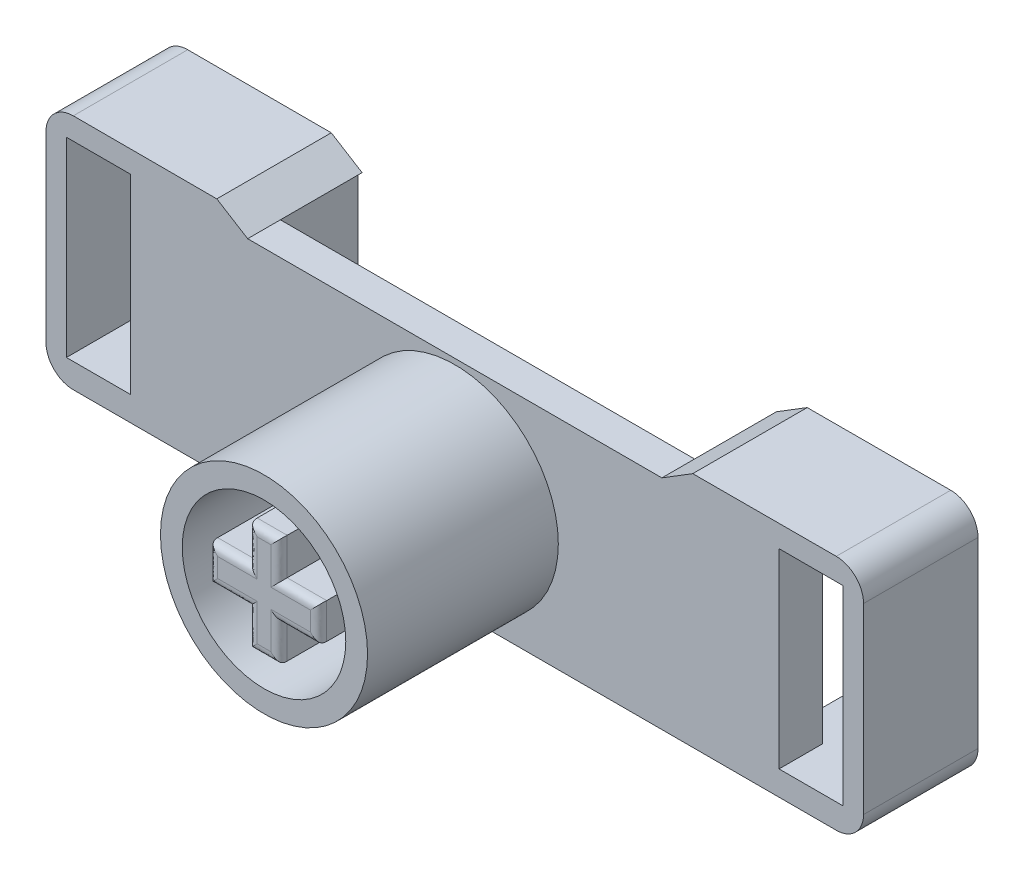
SolidWorks part; units mm, degrees
ref_plane "Front Plane" through (0, 0, 0) normal (0, 0, 1) x (1, 0, 0)
ref_plane "Top Plane" through (0, 0, 0) normal (0, 1, 0) x (1, 0, 0)
ref_plane "Right Plane" through (0, 0, 0) normal (1, 0, 0) x (0, 0, -1)
sketch "Cherry" plane through (0, 0, 0) normal (0, 0, 1) x (1, 0, 0)
  line L0 (0.55, 0.65) -> (2, 0.65)
  line L1 (-2, -0.65) -> (-0.55, -0.65)
  line L2 (-2, -0.65) -> (-2, 0.65)
  line L3 (-2, 0.65) -> (-0.55, 0.65)
  line L4 (2, -0.65) -> (2, 0.65)
  line L7 (-0.55, -2) -> (0.55, -2)
  line L8 (-0.55, -2) -> (-0.55, -0.65)
  line L9 (-0.55, 2) -> (0.55, 2)
  line L10 (0.55, -2) -> (0.55, -0.65)
  line L13 (0.55, 0.65) -> (0.55, 2)
  line L15 (0.55, -0.65) -> (2, -0.65)
  line L17 (-0.55, 0.65) -> (-0.55, 2)
  circle A0 centre (0, 0) radius 3
  circle A1 centre (0, 0) radius 3.8
  dimension "D1" = 1.3
  dimension "D2" = 4
  dimension "D3" = 1.1
  dimension "D4" = 4
extrude "Outer Cylinder" add sketch "Cherry" along normal blind 7 contours A1 A0 | L17 L3 L2 L1 L8 L7 L10 L15 L4 L0 L13 L9 region at (0, 0, 0) region at (-3.6925, 0, 0)
sketch "Inner Gap" plane through (0, 0, 0) normal (0, 0, 1) x (1, 0, 0)
  circle A0 centre (0, 0.0112) radius 3
extrude "Inner Wall" add sketch "Inner Gap" along normal blind 3
fillet "Fillet2" radius 0.3 12 edges at (-1.275, 0.65, 7) (-2, 0, 7) (-1.275, -0.65, 7) (-0.55, -1.325, 7) (0, -2, 7) (0.55, -1.325, 7) (1.275, -0.65, 7) (2, 0, 7) (1.275, 0.65, 7) (0.55, 1.325, 7) (0, 2, 7) (-0.55, 1.325, 7) curvature continuous yes
sketch "Sketch2" plane through (0, 0, 0) normal (0, 0, 1) x (1, 0, 0)
  line L5 (0, -1000) -> (0, 49000) construction
  line L6 (-1000, 0) -> (49000, 0) construction
  line L7 (-15, -996.1639) -> (-15, 49003.8361) construction
  line L8 (-11.55, -997.4571) -> (-11.55, 49002.5429) construction
  line L9 (-14.1, -997.5605) -> (-14.1, 49002.4395) construction
  line L10 (-7.6, -998.1554) -> (-7.6, 49001.8446) construction
  line L12 (-1001.5043, 4) -> (48998.4957, 4) construction
  line L14 (-1001.5043, -4) -> (48998.4957, -4) construction
  line L21 (-1004.1116, 4.7) -> (48995.8884, 4.7) construction
  line L22 (-15, -3) -> (-15, 3.706)
  line L24 (-13.9989, 4.706) -> (-8.7319, 4.7)
  line L28 (-7.6, 4) -> (7.6, 4)
  line L29 (-14, -4) -> (14, -4)
  line L30 (-8.6, -997.4752) -> (-8.6, 49002.5248) construction
  line L31 (-8.7319, 4.7) -> (-7.6, 4)
  line L32 (-1003.474, -3.1) -> (48996.526, -3.1) construction
  line L33 (-1010.3803, 3.8) -> (48989.6197, 3.8) construction
  line L38 (7.6, -998.1554) -> (7.6, 49001.8446) construction
  line L39 (8.6, -997.4752) -> (8.6, 49002.5248) construction
  line L40 (11.55, -997.4571) -> (11.55, 49002.5429) construction
  line L41 (14.1, -997.5605) -> (14.1, 49002.4395) construction
  line L42 (15, -996.1639) -> (15, 49003.8361) construction
  line L47 (8.7319, 4.7) -> (7.6, 4)
  line L48 (13.9989, 4.706) -> (8.7319, 4.7)
  line L49 (15, -3) -> (15, 3.706)
  arc A0 (15, -3) -> (14, -4) centre (14, -3) cw
  arc A1 (13.9989, 4.706) -> (15, 3.706) centre (14, 3.706) cw
  arc A2 (-15, -3) -> (-14, -4) centre (-14, -3) ccw
  arc A3 (-15, 3.706) -> (-13.9989, 4.706) centre (-14, 3.706) cw
  point P41 (0, 4)
  point P69 (0, -4)
  point P71 (15, -4)
  point P74 (15, 4.7072)
  point P77 (-15, -4)
  point P80 (-15, 4.7072)
  dimension "D1" = 15
  dimension "D10" = 1
  dimension "D2" = 0.9
  dimension "D3" = 2.55
  dimension "D4" = 7.4
  dimension "D5" = 4
  dimension "D6" = 4.7
  dimension "D7" = 1
  dimension "D8" = 0.9
  dimension "D9" = 0.9
extrude "Boss-Extrude1" add sketch "Sketch2" against normal blind 4.2
sketch "Sketch3" plane through (0, 0, 0) normal (0, 0, 1) x (1, 0, 0)
  line L1 (-2, -2) -> (2, -2) construction
  line L2 (-2, -2) -> (-2, 2) construction
  line L3 (-2, 2) -> (2, 2) construction
  line L4 (2, -2) -> (2, 2) construction
  line L5 (-2, -2) -> (2, 2) construction
  line L6 (-2, 2) -> (2, -2) construction
  line L7 (-2, 2) -> (-0.55, 2)
  line L8 (-2, 2) -> (-2, 0.65)
  line L9 (-2, 0.65) -> (-0.55, 0.65)
  line L10 (-0.55, 2) -> (-0.55, 0.65)
  line L11 (2, 2) -> (0.55, 2)
  line L12 (2, 2) -> (2, 0.65)
  line L13 (2, 0.65) -> (0.55, 0.65)
  line L14 (0.55, 2) -> (0.55, 0.65)
  line L15 (2, -2) -> (0.55, -2)
  line L16 (2, -2) -> (2, -0.65)
  line L17 (2, -0.65) -> (0.55, -0.65)
  line L18 (0.55, -2) -> (0.55, -0.65)
  line L19 (-2, -2) -> (-0.55, -2)
  line L20 (-2, -2) -> (-2, -0.65)
  line L21 (-2, -0.65) -> (-0.55, -0.65)
  line L22 (-0.55, -2) -> (-0.55, -0.65)
  spline S0 degree 3 poles (-0.25, 0.35) (-0.2972, 0.3993) (-0.3671, 0.4724) (-0.4721, 0.5698) (-0.5409, 0.6473) (-0.5468, 0.6491) (-0.55, 0.65) knots 0 0 0 0 0.340117 0.503355 0.734924 1 1 1 1 construction
  spline S1 degree 3 poles (0.25, 0.35) (0.2994, 0.3972) (0.3724, 0.4671) (0.4699, 0.5721) (0.5473, 0.6409) (0.5491, 0.6468) (0.55, 0.65) knots 0 0 0 0 0.340193 0.503487 0.734982 1 1 1 1 construction
  spline S2 degree 3 poles (0.55, -0.65) (0.5491, -0.6468) (0.5473, -0.6409) (0.4699, -0.5721) (0.3724, -0.4671) (0.2994, -0.3972) (0.25, -0.35) knots 0 0 0 0 0.265018 0.496513 0.659807 1 1 1 1 construction
  point P0 (0, 0)
  dimension "D1" = 4
  dimension "D2" = 4
  dimension "D3" = 1.3
  dimension "D4" = 1.1
sketch "Sketch5" plane through (0, 0, -4.2) normal (0, 0, -1) x (-1, 0, 0)
  line L0 (0, -1000) -> (0, 49000) construction
  line L1 (-7.75, -1000.8733) -> (-7.75, 48999.1267) construction
  line L2 (-1000.8968, 4) -> (48999.1032, 4) construction
  line L3 (-1000, 0) -> (49000, 0) construction
  line L4 (-1000.8968, -4) -> (48999.1032, -4) construction
  line L5 (7.75, -1000.8733) -> (7.75, 48999.1267) construction
  line L7 (-7.6, 4) -> (7.75, 4)
  line L8 (-7.6, 4) -> (-7.6, -4)
  line L9 (-7.6, -4) -> (7.75, -4)
  line L10 (7.75, 4) -> (7.75, -4)
  dimension "D1" = 4
  dimension "D2" = 7.75
extrude "Cut-Extrude7" cut sketch "Sketch3" against normal through all both and the other way through all
extrude "Cut-Extrude2" cut sketch "Sketch5" against normal blind 3
sketch "Sketch6" plane through (0, 0, 0) normal (0, 0, 1) x (1, 0, 0)
  line L0 (1010.3803, 3.9) -> (-48989.6197, 3.9) construction
  line L1 (-14.25, 3.9) -> (-11.9, 3.9)
  line L2 (-14.25, 3.9) -> (-14.25, -3.1)
  line L3 (-14.25, -3.1) -> (-11.9, -3.1)
  line L4 (-11.9, 3.9) -> (-11.9, -3.1)
  line L5 (0, -1000) -> (0, 49000) construction
  line L6 (-1000, 0) -> (49000, 0) construction
  line L7 (-15.15, -996.1639) -> (-15.15, 49003.8361) construction
  line L8 (-11.9, -997.4571) -> (-11.9, 49002.5429) construction
  line L9 (-14.25, -997.5605) -> (-14.25, 49002.4395) construction
  line L10 (-7.75, -998.1554) -> (-7.75, 49001.8446) construction
  line L11 (1003.474, -3.1) -> (-48996.526, -3.1) construction
  line L12 (-1001.5043, 4) -> (48998.4957, 4) construction
  line L13 (1001.5043, 4) -> (-48998.4957, 4) construction
  line L14 (-1001.5043, -4) -> (48998.4957, -4) construction
  line L16 (11.9, -997.4571) -> (11.9, 49002.5429) construction
  line L17 (1000, 0) -> (-49000, 0) construction
  line L18 (11.9, 3.9) -> (11.9, -3.1)
  line L19 (14.25, -3.1) -> (11.9, -3.1)
  line L20 (14.25, 3.9) -> (14.25, -3.1)
  line L21 (-1004.1116, 4.8) -> (48995.8884, 4.8) construction
  line L22 (14.25, 3.9) -> (11.9, 3.9)
  line L30 (-8.75, -997.4752) -> (-8.75, 49002.5248) construction
  line L32 (-1003.474, -3.1) -> (48996.526, -3.1) construction
  line L33 (-1010.3803, 3.9) -> (48989.6197, 3.9) construction
  line L38 (7.75, -998.1554) -> (7.75, 49001.8446) construction
  line L39 (8.75, -997.4752) -> (8.75, 49002.5248) construction
  line L41 (14.25, -997.5605) -> (14.25, 49002.4395) construction
  line L42 (15.15, -996.1639) -> (15.15, 49003.8361) construction
  point P41 (0, 4)
  point P69 (0, -4)
  point P71 (15.15, -4)
  point P74 (15.15, 4.8073)
  point P77 (-15.15, -4)
  point P80 (-15.15, 4.8073)
  dimension "D1" = 15.15
  dimension "D2" = 0.9
  dimension "D3" = 2.35
  dimension "D4" = 7.4
  dimension "D5" = 4
  dimension "D6" = 4.8
  dimension "D7" = 1
  dimension "D8" = 0.9
  dimension "D9" = 0.9
extrude "Cut-Extrude3" cut sketch "Sketch6" against normal blind 3.5
sketch "Sketch8" plane through (0, 0, -4.2) normal (0, 0, 1) x (1, 0, 0)
  line L0 (-1010.2744, 1.9) -> (48989.7256, 1.9) construction
  line L1 (-10.75, -1001.0626) -> (-10.75, 48998.9374) construction
  line L3 (-10.75, -4) -> (-10.75, -3.1)
  line L4 (-10.75, -3.1) -> (-12.25, -3.1)
  line L5 (0, -1000) -> (0, 49000) construction
  line L6 (-1000, 0) -> (49000, 0) construction
  line L7 (-15.15, -996.1639) -> (-15.15, 49003.8361) construction
  line L8 (-12.25, -997.4571) -> (-12.25, 49002.5429) construction
  line L9 (-14.25, -997.5605) -> (-14.25, 49002.4395) construction
  line L10 (-7.75, -998.1554) -> (-7.75, 49001.8446) construction
  line L11 (-12.25, -3.1) -> (-12.25, 1.9)
  line L12 (-12.25, 1.9) -> (-14.25, 1.9)
  line L13 (-10.75, -4) -> (-8.6534, -4)
  line L14 (-1001.5043, -4) -> (48998.4957, -4) construction
  line L15 (-14.25, 3.9) -> (-14.25, 1.9)
  line L16 (-14.25, 3.9) -> (-8.65, 3.9)
  line L18 (-8.65, 3.9) -> (-8.6534, -4)
  line L19 (8.65, 3.9) -> (8.6534, -4)
  line L21 (-1004.1116, 4.8) -> (48995.8884, 4.8) construction
  line L22 (14.25, 3.9) -> (8.65, 3.9)
  line L23 (14.25, 3.9) -> (14.25, 1.9)
  line L24 (10.75, -4) -> (8.6534, -4)
  line L25 (12.25, 1.9) -> (14.25, 1.9)
  line L27 (12.25, -3.1) -> (12.25, 1.9)
  line L28 (10.75, -3.1) -> (12.25, -3.1)
  line L29 (10.75, -4) -> (10.75, -3.1)
  line L30 (-8.65, -997.4752) -> (-8.65, 49002.5248) construction
  line L32 (-1003.474, -3.1) -> (48996.526, -3.1) construction
  line L33 (-1010.3803, 3.9) -> (48989.6197, 3.9) construction
  line L38 (7.75, -998.1554) -> (7.75, 49001.8446) construction
  line L39 (8.65, -997.4752) -> (8.65, 49002.5248) construction
  line L40 (12.25, -997.4571) -> (12.25, 49002.5429) construction
  line L41 (14.25, -997.5605) -> (14.25, 49002.4395) construction
  line L42 (15.15, -996.1639) -> (15.15, 49003.8361) construction
  point P69 (0, -4)
  point P71 (15.15, -4)
  point P74 (15.15, 4.8073)
  point P77 (-15.15, -4)
  point P80 (-15.15, 4.8073)
  dimension "D1" = 15.15
  dimension "D10" = 4.4
  dimension "D2" = 0.9
  dimension "D3" = 2.9
  dimension "D4" = 7.4
  dimension "D5" = 5.9
  dimension "D6" = 4.8
  dimension "D7" = 0.9
  dimension "D8" = 0.9
  dimension "D9" = 0.9
extrude "Cut-Extrude4" cut sketch "Sketch8" along normal blind 2.6
sketch "Sketch10" plane through (0, 0, -1.6) normal (0, 0, -1) x (-1, 0, 0)
  line L0 (-1010.2744, 1.9) -> (48989.7256, 1.9) construction
  line L1 (-11, -1001.0626) -> (-11, 48998.9374) construction
  line L2 (-10.75, -1002.0108) -> (-10.75, 48997.9892) construction
  line L3 (-10.75, -4) -> (-10.75, -3.1)
  line L4 (-10.75, -3.1) -> (-11, -3.1)
  line L5 (0, -1000) -> (0, 49000) construction
  line L6 (-1000, 0) -> (49000, 0) construction
  line L7 (-15.15, -996.1639) -> (-15.15, 49003.8361) construction
  line L8 (-11.9, -997.4571) -> (-11.9, 49002.5429) construction
  line L9 (-14.25, -997.5605) -> (-14.25, 49002.4395) construction
  line L10 (-7.75, -998.1554) -> (-7.75, 49001.8446) construction
  line L11 (-11, -3.1) -> (-11, 3.9)
  line L12 (-11, 3.9) -> (-8.65, 3.9)
  line L13 (-8.65, 3.9) -> (-8.6534, -4)
  line L14 (-1001.5043, -4) -> (48998.4957, -4) construction
  line L15 (-8.6534, -4) -> (-10.75, -4)
  line L16 (8.6534, -4) -> (10.75, -4)
  line L17 (8.65, 3.9) -> (8.6534, -4)
  line L18 (11, 3.9) -> (8.65, 3.9)
  line L19 (11, -3.1) -> (11, 3.9)
  line L20 (10.75, -3.1) -> (11, -3.1)
  line L21 (-1004.1116, 4.8) -> (48995.8884, 4.8) construction
  line L22 (10.75, -4) -> (10.75, -3.1)
  line L30 (-8.65, -997.4752) -> (-8.65, 49002.5248) construction
  line L32 (-1003.474, -3.1) -> (48996.526, -3.1) construction
  line L33 (-1010.3803, 3.9) -> (48989.6197, 3.9) construction
  line L38 (7.75, -998.1554) -> (7.75, 49001.8446) construction
  line L39 (8.65, -997.4752) -> (8.65, 49002.5248) construction
  line L40 (11.9, -997.4571) -> (11.9, 49002.5429) construction
  line L41 (14.25, -997.5605) -> (14.25, 49002.4395) construction
  line L42 (15.15, -996.1639) -> (15.15, 49003.8361) construction
  point P69 (0, -4)
  point P71 (15.15, -4)
  point P74 (15.15, 4.8073)
  point P77 (-15.15, -4)
  point P80 (-15.15, 4.8073)
  dimension "D1" = 15.15
  dimension "D10" = 0.9
  dimension "D2" = 0.9
  dimension "D3" = 2.35
  dimension "D4" = 7.4
  dimension "D5" = 5.9
  dimension "D6" = 4.8
  dimension "D7" = 0.9
  dimension "D8" = 0.9
  dimension "D9" = 0.9
  dimension "D11" = 4.4
extrude "Cut-Extrude5" cut sketch "Sketch10" against normal blind 0.4
